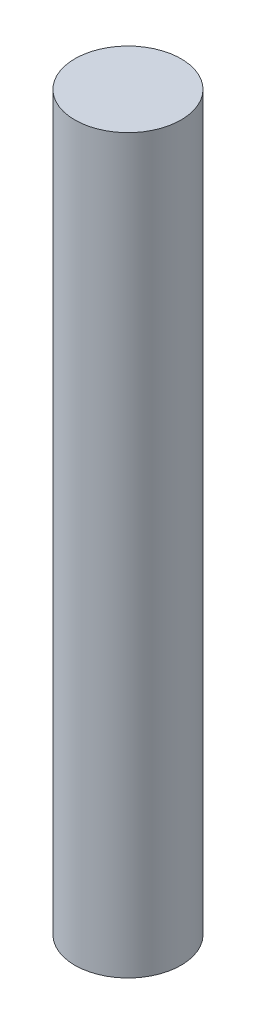
SolidWorks part; units mm, degrees
ref_plane "Front Plane" through (0, 0, 0) normal (0, 0, 1) x (1, 0, 0)
ref_plane "Top Plane" through (0, 0, 0) normal (0, 1, 0) x (1, 0, 0)
ref_plane "Right Plane" through (0, 0, 0) normal (1, 0, 0) x (0, 0, -1)
sketch "Sketch1" plane through (0, 0, 0) normal (0, 1, 0) x (1, 0, 0)
  circle A0 centre (0, 0) radius 2.9
  dimension "D1" = 5.8
extrude "Boss-Extrude1" add sketch "Sketch1" along normal blind 40
